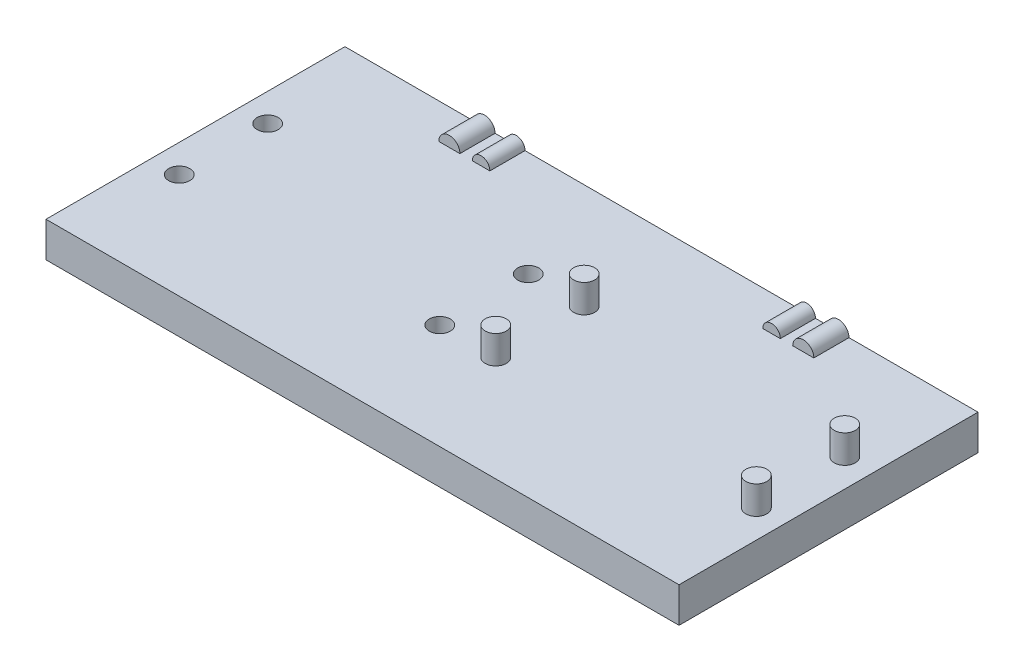
SolidWorks part; units mm, degrees
ref_plane "Piano frontale" through (0, 0, 0) normal (0, 0, 1) x (1, 0, 0)
ref_plane "Piano superiore" through (0, 0, 0) normal (0, 1, 0) x (1, 0, 0)
ref_plane "Piano destro" through (0, 0, 0) normal (1, 0, 0) x (0, 0, -1)
sketch "Schizzo1" plane through (0, 0, 0) normal (0, 1, 0) x (1, 0, 0)
  line L1 (-90, 42.5) -> (90, 42.5)
  line L2 (-90, 42.5) -> (-90, -42.5)
  line L3 (-90, -42.5) -> (90, -42.5)
  line L4 (90, 42.5) -> (90, -42.5)
  dimension "D1" = 180
  dimension "D2" = 85
extrude "Estrusione-Estrusione1" add sketch "Schizzo1" along normal blind 10
sketch "Schizzo5" plane through (0, 10, 0) normal (0, 1, 0) x (1, 0, 0)
  line L0 (0, 56.7701) -> (0, -66.2979) construction
  line L1 (-100.8364, 0) -> (102.1597, 0) construction
  line L2 (90, 42.5) -> (-90, 42.5) construction
  line L3 (-90, 42.5) -> (0, 42.5) construction
  line L4 (-45, 56.7701) -> (-45, -52.2708) construction
  circle A0 centre (-82.0453, 12.5715) radius 3
  circle A1 centre (-82.0453, -12.5715) radius 3
  circle A2 centre (-7.9547, -12.5715) radius 3
  circle A3 centre (-7.9547, 12.5715) radius 3
  circle A4 centre (82.0453, -12.5715) radius 3
  circle A5 centre (82.0453, 12.5715) radius 3
  circle A6 centre (7.9547, -12.5715) radius 3
  circle A7 centre (7.9547, 12.5715) radius 3
  dimension "D1" = 6
extrude "Estrusione-Estrusione3" add sketch "Schizzo5" along normal blind 8 contours A7 | A6 | A4 | A5
extrude "Taglio-Estrusione1" cut sketch "Schizzo5<3>" against normal blind 8 contours A0 | A1 | A2 | A3
sketch "Schizzo5<3>" plane through (0, 10, 0) normal (0, 1, 0) x (1, 0, 0) same geometry as "Schizzo5"
sketch "Schizzo6" plane through (0, 0, -42.5) normal (0, 0, -1) x (-1, 0, 0)
  line L0 (-53.3192, 10) -> (-47.3192, 10)
  line L2 (-43.7947, 10) -> (-38.7947, 10)
  line L3 (-79.0453, 10) -> (-10.9547, 10) construction
  line L4 (0, 37.6792) -> (0, -22.211) construction
  line L5 (43.7947, 10) -> (38.7947, 10)
  line L6 (53.3192, 10) -> (47.3192, 10)
  arc A0 (-53.3192, 10) -> (-47.3192, 10) centre (-50.3192, 10) cw
  arc A1 (-43.7947, 10) -> (-38.7947, 10) centre (-41.2947, 10) cw
  arc A2 (43.7947, 10) -> (38.7947, 10) centre (41.2947, 10) ccw
  arc A3 (53.3192, 10) -> (47.3192, 10) centre (50.3192, 10) ccw
  dimension "D1" = 3
  dimension "D2" = 2.5
extrude "Estrusione-Estrusione4" add sketch "Schizzo6" against normal blind 10
